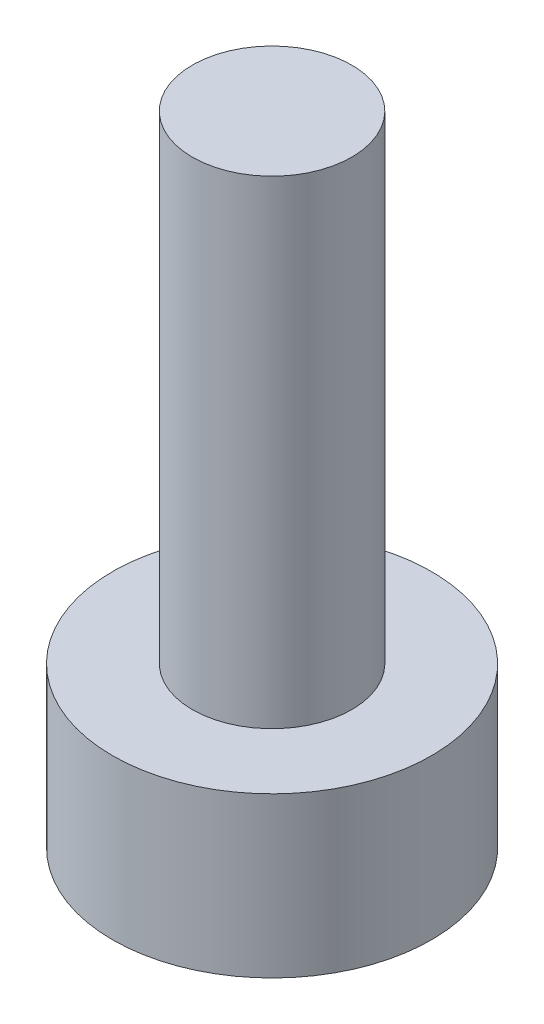
SolidWorks part; units mm, degrees
ref_plane "Front Plane" through (0, 0, 0) normal (0, 0, 1) x (1, 0, 0)
ref_plane "Top Plane" through (0, 0, 0) normal (0, 1, 0) x (1, 0, 0)
ref_plane "Right Plane" through (0, 0, 0) normal (1, 0, 0) x (0, 0, -1)
sketch "Sketch1" plane through (0, 0, 0) normal (0, 1, 0) x (1, 0, 0)
  circle A0 centre (0, 0) radius 2
  circle A1 centre (0, 0) radius 1
  dimension "D1" = 2
  dimension "D2" = 4
extrude "Boss-Extrude1" add sketch "Sketch1" along normal blind 2 contours A0
extrude "Boss-Extrude2" add sketch "Sketch1<3>" along normal blind 8 contours A1
sketch "Sketch1<3>" plane through (0, 0, 0) normal (0, 1, 0) x (1, 0, 0) same geometry as "Sketch1"
